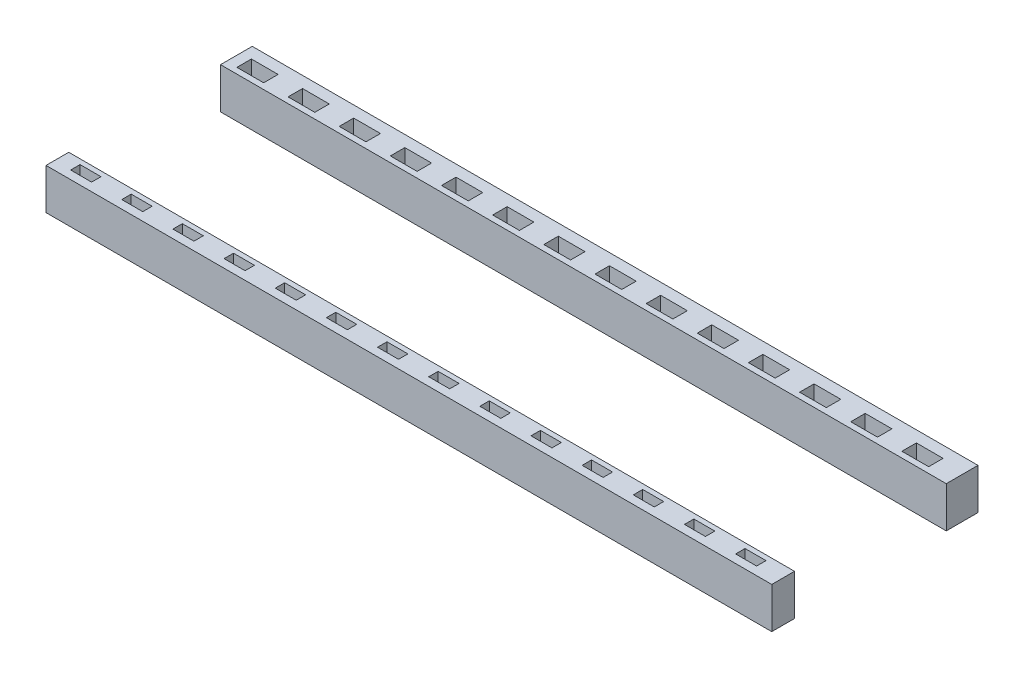
SolidWorks part; units mm, degrees
ref_plane "Alzado" through (0, 0, 0) normal (0, 0, 1) x (1, 0, 0)
ref_plane "Planta" through (0, 0, 0) normal (0, 1, 0) x (1, 0, 0)
ref_plane "Vista lateral" through (0, 0, 0) normal (1, 0, 0) x (0, 0, -1)
sketch "Croquis1" plane through (0, 32.4682, 0) normal (0, 1, 0) x (1, 0, 0)
  line L0 (14.176, -55.943) -> (49.6465, -55.943)
  line L1 (49.6465, -55.943) -> (49.6465, -57.494)
  line L2 (49.6465, -57.494) -> (14.176, -57.494)
  line L3 (14.176, -57.494) -> (14.176, -55.943)
  line L4 (14.176, -64.9103) -> (14.176, -66.0225)
  line L5 (14.176, -66.0225) -> (49.6465, -66.0225)
  line L6 (49.6465, -66.0225) -> (49.6465, -64.9103)
  line L7 (49.6465, -64.9103) -> (14.176, -64.9103)
  line L8 (14.176, -64.9103) -> (14.0941, -64.7867)
  line L9 (18.4978, -56.4999) -> (18.4978, -57.2066)
  line L10 (14.6905, -56.4999) -> (15.9978, -56.4999)
  line L11 (14.6905, -56.4999) -> (14.6905, -57.2066)
  line L12 (14.6905, -57.2066) -> (15.9978, -57.2066)
  line L13 (15.9978, -56.4999) -> (15.9978, -57.2066)
  line L14 (14.9731, -65.1563) -> (15.9978, -65.1563)
  line L15 (14.9731, -65.1563) -> (14.9731, -65.6156)
  line L16 (14.9731, -65.6156) -> (15.9978, -65.6156)
  line L17 (15.9978, -65.1563) -> (15.9978, -65.6156)
  line L18 (17.1905, -56.4999) -> (18.4978, -56.4999)
  line L19 (17.1905, -56.4999) -> (17.1905, -57.2066)
  line L20 (17.1905, -57.2066) -> (18.4978, -57.2066)
  line L21 (17.4731, -65.1563) -> (18.4978, -65.1563)
  line L22 (17.4731, -65.6156) -> (18.4978, -65.6156)
  line L23 (17.4731, -65.1563) -> (17.4731, -65.6156)
  line L24 (18.4978, -65.1563) -> (18.4978, -65.6156)
  line L25 (20.9978, -56.4999) -> (20.9978, -57.2066)
  line L26 (19.6905, -56.4999) -> (20.9978, -56.4999)
  line L27 (19.6905, -56.4999) -> (19.6905, -57.2066)
  line L28 (19.6905, -57.2066) -> (20.9978, -57.2066)
  line L29 (19.9731, -65.1563) -> (20.9978, -65.1563)
  line L30 (19.9731, -65.6156) -> (20.9978, -65.6156)
  line L31 (19.9731, -65.1563) -> (19.9731, -65.6156)
  line L32 (20.9978, -65.1563) -> (20.9978, -65.6156)
  line L33 (23.4978, -56.4999) -> (23.4978, -57.2066)
  line L34 (22.1905, -56.4999) -> (23.4978, -56.4999)
  line L35 (22.1905, -56.4999) -> (22.1905, -57.2066)
  line L36 (22.1905, -57.2066) -> (23.4978, -57.2066)
  line L37 (22.4731, -65.1563) -> (23.4978, -65.1563)
  line L38 (22.4731, -65.6156) -> (23.4978, -65.6156)
  line L39 (22.4731, -65.1563) -> (22.4731, -65.6156)
  line L40 (23.4978, -65.1563) -> (23.4978, -65.6156)
  line L41 (25.9978, -56.4999) -> (25.9978, -57.2066)
  line L42 (24.6905, -56.4999) -> (25.9978, -56.4999)
  line L43 (24.6905, -56.4999) -> (24.6905, -57.2066)
  line L44 (24.6905, -57.2066) -> (25.9978, -57.2066)
  line L45 (24.9731, -65.1563) -> (25.9978, -65.1563)
  line L46 (24.9731, -65.6156) -> (25.9978, -65.6156)
  line L47 (24.9731, -65.1563) -> (24.9731, -65.6156)
  line L48 (25.9978, -65.1563) -> (25.9978, -65.6156)
  line L49 (28.4978, -56.4999) -> (28.4978, -57.2066)
  line L50 (27.1905, -56.4999) -> (28.4978, -56.4999)
  line L51 (27.1905, -56.4999) -> (27.1905, -57.2066)
  line L52 (27.1905, -57.2066) -> (28.4978, -57.2066)
  line L53 (27.4731, -65.1563) -> (28.4978, -65.1563)
  line L54 (27.4731, -65.6156) -> (28.4978, -65.6156)
  line L55 (27.4731, -65.1563) -> (27.4731, -65.6156)
  line L56 (28.4978, -65.1563) -> (28.4978, -65.6156)
  line L57 (30.9978, -56.4999) -> (30.9978, -57.2066)
  line L58 (29.6905, -56.4999) -> (30.9978, -56.4999)
  line L59 (29.6905, -56.4999) -> (29.6905, -57.2066)
  line L60 (29.6905, -57.2066) -> (30.9978, -57.2066)
  line L61 (29.9731, -65.1563) -> (30.9978, -65.1563)
  line L62 (29.9731, -65.6156) -> (30.9978, -65.6156)
  line L63 (29.9731, -65.1563) -> (29.9731, -65.6156)
  line L64 (30.9978, -65.1563) -> (30.9978, -65.6156)
  line L65 (33.4978, -56.4999) -> (33.4978, -57.2066)
  line L66 (32.1905, -56.4999) -> (33.4978, -56.4999)
  line L67 (32.1905, -56.4999) -> (32.1905, -57.2066)
  line L68 (32.1905, -57.2066) -> (33.4978, -57.2066)
  line L69 (32.4731, -65.1563) -> (33.4978, -65.1563)
  line L70 (32.4731, -65.6156) -> (33.4978, -65.6156)
  line L71 (32.4731, -65.1563) -> (32.4731, -65.6156)
  line L72 (33.4978, -65.1563) -> (33.4978, -65.6156)
  line L73 (35.9978, -56.4999) -> (35.9978, -57.2066)
  line L74 (34.6905, -56.4999) -> (35.9978, -56.4999)
  line L75 (34.6905, -56.4999) -> (34.6905, -57.2066)
  line L76 (34.6905, -57.2066) -> (35.9978, -57.2066)
  line L77 (34.9731, -65.1563) -> (35.9978, -65.1563)
  line L78 (34.9731, -65.6156) -> (35.9978, -65.6156)
  line L79 (34.9731, -65.1563) -> (34.9731, -65.6156)
  line L80 (35.9978, -65.1563) -> (35.9978, -65.6156)
  line L81 (38.4978, -56.4999) -> (38.4978, -57.2066)
  line L82 (37.1905, -56.4999) -> (38.4978, -56.4999)
  line L83 (37.1905, -56.4999) -> (37.1905, -57.2066)
  line L84 (37.1905, -57.2066) -> (38.4978, -57.2066)
  line L85 (37.4731, -65.1563) -> (38.4978, -65.1563)
  line L86 (37.4731, -65.6156) -> (38.4978, -65.6156)
  line L87 (37.4731, -65.1563) -> (37.4731, -65.6156)
  line L88 (38.4978, -65.1563) -> (38.4978, -65.6156)
  line L89 (40.9978, -56.4999) -> (40.9978, -57.2066)
  line L90 (39.6905, -56.4999) -> (40.9978, -56.4999)
  line L91 (39.6905, -56.4999) -> (39.6905, -57.2066)
  line L92 (39.6905, -57.2066) -> (40.9978, -57.2066)
  line L93 (39.9731, -65.1563) -> (40.9978, -65.1563)
  line L94 (39.9731, -65.6156) -> (40.9978, -65.6156)
  line L95 (39.9731, -65.1563) -> (39.9731, -65.6156)
  line L96 (40.9978, -65.1563) -> (40.9978, -65.6156)
  line L97 (43.4978, -56.4999) -> (43.4978, -57.2066)
  line L98 (42.1905, -56.4999) -> (43.4978, -56.4999)
  line L99 (42.1905, -56.4999) -> (42.1905, -57.2066)
  line L100 (42.1905, -57.2066) -> (43.4978, -57.2066)
  line L101 (42.4731, -65.1563) -> (43.4978, -65.1563)
  line L102 (42.4731, -65.6156) -> (43.4978, -65.6156)
  line L103 (42.4731, -65.1563) -> (42.4731, -65.6156)
  line L104 (43.4978, -65.1563) -> (43.4978, -65.6156)
  line L105 (45.9978, -56.4999) -> (45.9978, -57.2066)
  line L106 (44.6905, -56.4999) -> (45.9978, -56.4999)
  line L107 (44.6905, -56.4999) -> (44.6905, -57.2066)
  line L108 (44.6905, -57.2066) -> (45.9978, -57.2066)
  line L109 (44.9731, -65.1563) -> (45.9978, -65.1563)
  line L110 (44.9731, -65.6156) -> (45.9978, -65.6156)
  line L111 (44.9731, -65.1563) -> (44.9731, -65.6156)
  line L112 (45.9978, -65.1563) -> (45.9978, -65.6156)
  line L113 (48.4978, -56.4999) -> (48.4978, -57.2066)
  line L114 (47.1905, -56.4999) -> (48.4978, -56.4999)
  line L115 (47.1905, -56.4999) -> (47.1905, -57.2066)
  line L116 (47.1905, -57.2066) -> (48.4978, -57.2066)
  line L117 (47.4731, -65.1563) -> (48.4978, -65.1563)
  line L118 (47.4731, -65.6156) -> (48.4978, -65.6156)
  line L119 (47.4731, -65.1563) -> (47.4731, -65.6156)
  line L120 (48.4978, -65.1563) -> (48.4978, -65.6156)
  line L121 (15.9978, -56.4999) -> (18.4978, -56.4999) construction
  dimension "D2" = 2.5
  dimension "D1" = 14
extrude "Saliente-Extruir1" add sketch "Croquis1" along normal blind 2 contours L3 L2 L1 L0 L116 L115 L114 L113 L108 L107 L106 L105 L100 L99 L98 L97 L92 L91 L90 L89 L84 L83 L82 L81 L76 L75 L74 L73 L68 L67 L66 L65 L60 L59 L58 L57 L52 L51 L50 L49 L44 | L6 L7 L4 L5 L109 L112 L110 L111 L93 L96 L94 L95 L77 L80 L78 L79 L61 L64 L62 L63 L45 L48 L46 L47 L29 L32 L30 L31 L14 L17 L16 L15 L21 L24 L22 L23 L37 L40 L38 L39 L53 region at (32.0086, 32.4682, 56.677) region at (31.9464, 32.4682, 65.4826)
extrude "Saliente-Extruir2" add sketch "Croquis1<3>" along normal blind 1 contours L13 L10 L11 L12 | L19 L20 L9 L18 | L27 L28 L25 L26 | L35 L36 L33 L34 | L43 L44 L41 L42 | L51 L52 L49 L50 | L67 L68 L65 L66 | L75 L76 L73 L74 | L83 L84 L81 L82 | L91 L92 L89 L90 | L99 L100 L97 L98 | L115 L116 L113 L114 | L96 L93 L95 L94 | L88 L85 L87 L86 | L72 L69 L71 L70 | L64 L61 L63 L62 | L56 L53 L55 L54 | L48 L45 L47 L46 | L40 L37 L39 L38 | L32 L29 L31 L30 | L24 L21 L23 L22 | L17 L14 L15 L16 | L35 L36 L33 L34 | L60 L57 L58 L59 | L108 L105 L106 L107 | L117 L120 L118 L119 | L110 L112 L109 L111 | L101 L104 L102 L103 | L77 L80 L78 L79 | L24 L22 L23 L21 region at (17.8441, 32.4682, 56.8533) region at (15.3441, 32.4682, 56.8533) region at (15.4855, 32.4682, 65.3859) region at (17.9855, 32.4682, 65.3859) region at (20.3441, 32.4682, 56.8533) region at (20.4855, 32.4682, 65.3859) region at (22.8441, 32.4682, 56.8533) region at (22.9855, 32.4682, 65.3859) region at (25.3441, 32.4682, 56.8533) region at (25.4855, 32.4682, 65.3859) region at (27.8441, 32.4682, 56.8533) region at (27.9855, 32.4682, 65.3859) region at (30.4855, 32.4682, 65.3859) region at (32.8441, 32.4682, 56.8533) region at (32.9855, 32.4682, 65.3859) region at (35.3441, 32.4682, 56.8533) region at (37.8441, 32.4682, 56.8533) region at (37.9855, 32.4682, 65.3859) region at (40.3441, 32.4682, 56.8533) region at (40.4855, 32.4682, 65.3859) region at (42.8441, 32.4682, 56.8533) region at (47.8441, 32.4682, 56.8533)
sketch "Croquis1<3>" plane through (0, 32.4682, 0) normal (0, 1, 0) x (1, 0, 0) same geometry as "Croquis1"
